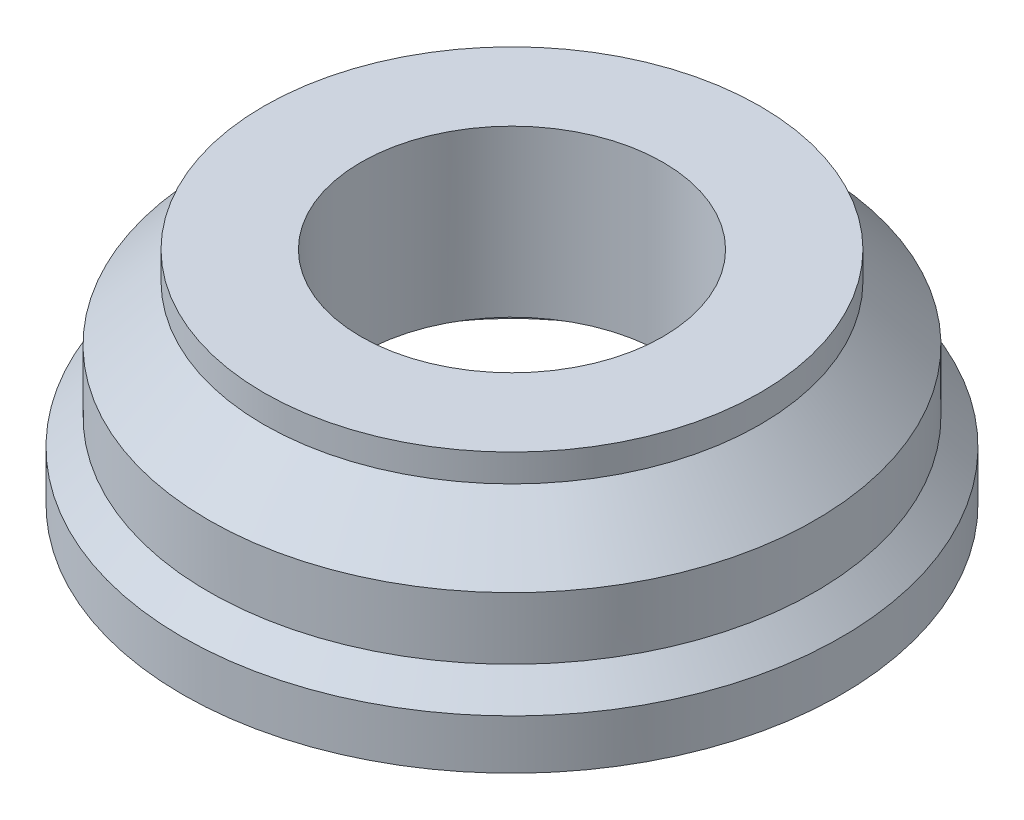
SolidWorks part; units mm, degrees
material "ABS"
ref_plane "Płaszczyzna przednia" through (0, 0, 0) normal (0, 0, 1) x (1, 0, 0)
ref_plane "Płaszczyzna górna" through (0, 0, 0) normal (0, 1, 0) x (1, 0, 0)
ref_plane "Płaszczyzna prawa" through (0, 0, 0) normal (1, 0, 0) x (0, 0, -1)
sketch "Szkic1" plane through (0, 0, 0) normal (0, 1, 0) x (1, 0, 0)
  line L0 (-50.0173, 36.2315) -> (-65.0121, 36.2315)
  line L1 (-30.6265, 36.7315) -> (-50.0173, 36.7315) construction
  line L2 (-30.6265, 36.7315) -> (-26.3173, 32.4223) construction
  line L3 (-30.6265, -6.2685) -> (-26.3173, -1.9594) construction
  line L4 (-69.0173, 26.2259) -> (-69.0173, 4.237)
  line L5 (-69.5173, 26.2259) -> (-69.5173, 4.237) construction
  line L6 (-50.0173, -5.7685) -> (-65.0121, -5.7685)
  line L7 (-50.0173, -5.7685) -> (-30.8336, -5.7685)
  line L8 (-30.8336, -5.7685) -> (-26.8173, -1.7523)
  line L9 (-50.0173, -6.2685) -> (-30.6265, -6.2685) construction
  line L10 (-26.8173, -1.7523) -> (-26.8173, 32.2152)
  line L11 (-26.3173, -1.9594) -> (-26.3173, 32.4223) construction
  line L12 (-50.0173, 36.7315) -> (-65.224, 36.7315) construction
  line L13 (-50.0173, -6.2685) -> (-65.224, -6.2685) construction
  line L14 (-30.8336, 36.2315) -> (-26.8173, 32.2152)
  line L15 (-30.8336, 36.2315) -> (-50.0173, 36.2315)
  circle A0 centre (-63.5173, -0.2685) radius 1.65
  circle A1 centre (-32.5173, -0.2685) radius 1.65
  circle A2 centre (-32.5173, 30.7315) radius 1.65
  circle A3 centre (-63.5173, 30.7315) radius 1.65
  circle A4 centre (-48.0173, 15.2315) radius 9.3 construction
  arc A5 (-65.0121, 36.2315) -> (-69.0173, 26.2259) centre (-54.5173, 26.2259) ccw
  arc A6 (-69.0173, 4.237) -> (-65.0121, -5.7685) centre (-54.5173, 4.237) ccw
  circle A7 centre (-48.0173, 15.2315) radius 9
  circle A8 centre (-48.0173, 15.2315) radius 11
  circle A9 centre (-48.0173, 15.2315) radius 11.95
  arc A11 (-65.224, 36.7315) -> (-69.5173, 26.2259) centre (-54.5173, 26.2259) ccw construction
  arc A12 (-69.5173, 4.237) -> (-65.224, -6.2685) centre (-54.5173, 4.237) ccw construction
  circle A18 centre (-48.0173, 15.2315) radius 5.4773
  circle A19 centre (-48.0173, 15.2315) radius 11.3 construction
  circle A20 centre (-48.0173, 15.2315) radius 12.25 construction
  circle A21 centre (-48.0173, 15.2315) radius 2.5 construction
  dimension "D1" = 0.5
  dimension "D2" = 0.3
  dimension "D3" = 0.3
  dimension "D4" = 0.3
extrude "Dodanie-wyciągnięcie1" add sketch "Szkic1" along normal blind 8 contours A7 A18 region at (-56.7628, 0, -15.2315)
extrude "Dodanie-wyciągnięcie2" add sketch "Szkic1<3>" along normal blind 7 contours A8 A7 region at (-58.7062, 0, -15.2315)
sketch "Szkic1<3>" plane through (0, 0, 0) normal (0, 1, 0) x (1, 0, 0) same geometry as "Szkic1"
extrude "Dodanie-wyciągnięcie3" add sketch "Szkic1<4>" along normal blind 3 contours A9 A8 region at (-59.6293, 0, -15.2315)
sketch "Szkic1<4>" plane through (0, 0, 0) normal (0, 1, 0) x (1, 0, 0) same geometry as "Szkic1"
extrude "Dodanie-wyciągnięcie4" add sketch "Szkic1<5>" against normal blind 3 contours L4 A6 L6 L7 L8 L10 L14 L15 L0 A5 A9 A0 A1 A2 A3 | A9 A8 | A8 A7 | A7 A18 region at (-40.4254, 0, -35.6361) region at (-56.7628, 0, -15.2315) region at (-58.7062, 0, -15.2315) region at (-59.6293, 0, -15.2315)
sketch "Szkic1<5>" plane through (0, 0, 0) normal (0, 1, 0) x (1, 0, 0) same geometry as "Szkic1"
sketch "Szkic2" plane through (0, -3, 0) normal (0, -1, 0) x (1, 0, 0)
  circle A0 centre (-48.0173, -15.2315) radius 8.25
  dimension "D1" = 16.5
extrude "Wytnij-wyciągnięcie1" cut sketch "Szkic2" against normal blind 5
chamfer "Sfazowanie1" distance 1.2 angle 45 1 edges at (-48.0173, 3, -3.2815)
sketch "Szkic3" plane through (0, -3, 0) normal (0, -1, 0) x (1, 0, 0)
  line L0 (-69.0173, -26.2259) -> (-36.8173, -26.2259)
  line L1 (-36.8173, -26.2259) -> (-36.8173, -4.237)
  line L2 (-36.8173, -4.237) -> (-69.0173, -4.237)
  line L4 (-26.8173, 1.7523) -> (-26.8173, -32.2152) construction
  line L11 (-69.0173, -4.237) -> (-69.0173, -26.2259)
  line L12 (-65.0121, -36.2315) -> (-30.8336, -36.2315)
  line L13 (-30.8336, -36.2315) -> (-26.8173, -32.2152)
  line L14 (-26.8173, -32.2152) -> (-26.8173, 1.7523)
  line L15 (-26.8173, 1.7523) -> (-30.8336, 5.7685)
  line L16 (-30.8336, 5.7685) -> (-65.0121, 5.7685)
  line L18 (-65.0121, -36.2315) -> (-30.8336, -36.2315)
  line L19 (-30.8336, -36.2315) -> (-26.8173, -32.2152)
  line L20 (-26.8173, -32.2152) -> (-26.8173, 1.7523)
  line L21 (-26.8173, 1.7523) -> (-30.8336, 5.7685)
  line L22 (-30.8336, 5.7685) -> (-65.0121, 5.7685)
  circle A0 centre (-63.5173, 0.2685) radius 1.65 construction
  circle A1 centre (-32.5173, 0.2685) radius 1.65 construction
  arc A2 (-69.0173, -26.2259) -> (-65.0121, -36.2315) centre (-54.5173, -26.2259) ccw
  arc A3 (-65.0121, 5.7685) -> (-69.0173, -4.237) centre (-54.5173, -4.237) ccw
  arc A4 (-69.0173, -26.2259) -> (-65.0121, -36.2315) centre (-54.5173, -26.2259) ccw
  arc A5 (-65.0121, 5.7685) -> (-69.0173, -4.237) centre (-54.5173, -4.237) ccw
  circle A6 centre (-32.5173, -30.7315) radius 1.65 construction
  circle A7 centre (-63.5173, -30.7315) radius 1.65 construction
  circle A8 centre (-63.5173, 0.2685) radius 1.65
  circle A9 centre (-32.5173, 0.2685) radius 1.65
  circle A10 centre (-32.5173, -30.7315) radius 1.65
  circle A11 centre (-63.5173, -30.7315) radius 1.65
  dimension "D1" = 10
  dimension "D2" = 0
extrude "Dodanie-wyciągnięcie5" add sketch "Szkic3" along normal blind 17
fillet "Zaokrąglenie1" radius 10 2 edges at (-36.8173, -11.5, -26.2259) (-36.8173, -11.5, -4.237)
fillet "Zaokrąglenie2" radius 4 8 edges at (-30.8336, -10, 5.7685) (-26.8173, -10, 1.7523) (-26.8173, -10, -32.2152) (-30.8336, -10, -36.2315) (-65.0121, -10, -36.2315) (-65.0121, -10, 5.7685) (-69.0173, -11.5, -26.2259) (-69.0173, -11.5, -4.237)
chamfer "Sfazowanie2" distance 2 angle 45 1 edges at (-48.0173, 7, -4.2315)
sketch "Szkic5" plane through (0, 0, 0) normal (0, 1, 0) x (1, 0, 0)
  line L6 (-63.1303, -5.7685) -> (-32.4904, -5.7685)
  line L7 (-29.662, -4.597) -> (-27.9889, -2.9239)
  line L8 (-26.8173, -0.0955) -> (-26.8173, 30.5584)
  line L9 (-27.9889, 33.3868) -> (-29.662, 35.0599)
  line L10 (-32.4904, 36.2315) -> (-63.1303, 36.2315)
  line L11 (-69.0173, 26.2259) -> (-69.0173, 4.237)
  line L12 (-63.1303, -5.7685) -> (-32.4904, -5.7685)
  line L13 (-29.662, -4.597) -> (-27.9889, -2.9239)
  line L14 (-26.8173, -0.0955) -> (-26.8173, 30.5584)
  line L15 (-27.9889, 33.3868) -> (-29.662, 35.0599)
  line L16 (-32.4904, 36.2315) -> (-63.1303, 36.2315)
  line L17 (-69.0173, 26.2259) -> (-69.0173, 4.237)
  arc A8 (-32.4904, -5.7685) -> (-29.662, -4.597) centre (-32.4904, -1.7685) ccw
  arc A9 (-27.9889, -2.9239) -> (-26.8173, -0.0955) centre (-30.8173, -0.0955) ccw
  arc A10 (-26.8173, 30.5584) -> (-27.9889, 33.3868) centre (-30.8173, 30.5584) ccw
  arc A11 (-29.662, 35.0599) -> (-32.4904, 36.2315) centre (-32.4904, 32.2315) ccw
  arc A12 (-63.1303, 36.2315) -> (-66.4115, 34.5193) centre (-63.1303, 32.2315) ccw
  arc A13 (-66.4115, 34.5193) -> (-69.0173, 26.2259) centre (-54.5173, 26.2259) ccw
  arc A14 (-69.0173, 4.237) -> (-66.4115, -4.0564) centre (-54.5173, 4.237) ccw
  arc A15 (-66.4115, -4.0564) -> (-63.1303, -5.7685) centre (-63.1303, -1.7685) ccw
  arc A16 (-32.4904, -5.7685) -> (-29.662, -4.597) centre (-32.4904, -1.7685) ccw
  arc A17 (-27.9889, -2.9239) -> (-26.8173, -0.0955) centre (-30.8173, -0.0955) ccw
  arc A18 (-26.8173, 30.5584) -> (-27.9889, 33.3868) centre (-30.8173, 30.5584) ccw
  arc A19 (-29.662, 35.0599) -> (-32.4904, 36.2315) centre (-32.4904, 32.2315) ccw
  arc A20 (-63.1303, 36.2315) -> (-66.4115, 34.5193) centre (-63.1303, 32.2315) ccw
  arc A21 (-66.4115, 34.5193) -> (-69.0173, 26.2259) centre (-54.5173, 26.2259) ccw
  arc A22 (-69.0173, 4.237) -> (-66.4115, -4.0564) centre (-54.5173, 4.237) ccw
  arc A23 (-66.4115, -4.0564) -> (-63.1303, -5.7685) centre (-63.1303, -1.7685) ccw
  dimension "D1" = 0
extrude "Wytnij-wyciągnięcie3" cut sketch "Szkic5" against normal through all
